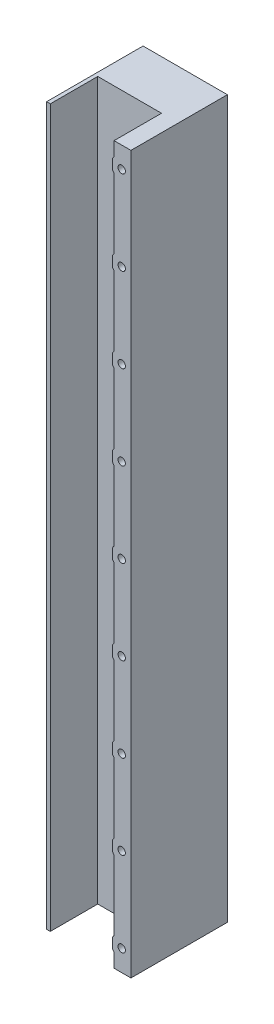
SolidWorks part; units mm, degrees
ref_plane "Top" through (0, 0, 0) normal (0, 0, 1) x (1, 0, 0)
ref_plane "Front" through (0, 0, 0) normal (0, 1, 0) x (1, 0, 0)
ref_plane "Right" through (0, 0, 0) normal (1, 0, 0) x (0, 0, -1)
sketch "Profile Sketch" plane through (0.0456, 0, -0.0242) normal (0, 1, 0) x (-1, 0, 0)
  line L1 (16.0456, 0.0242) -> (0.0456, 0.0242)
  line L2 (0.0456, 0.0242) -> (0.0456, -18.2758)
  line L3 (0.0456, -18.2758) -> (16.0456, -18.2758)
  line L5 (16.0456, -18.2758) -> (16.0456, 0.0242)
  line L12 (16.0456, 0.3949) -> (16.0456, 1.3939) construction
  line L13 (1.7956, 0.0242) -> (1.7956, 4.0449) construction
  dimension "D2" = 1.75
  dimension "Reel Width" = 16
  dimension "Height" = 18.3
extrude "Profile Extrude" add sketch "Profile Sketch" along normal blind 136
sketch "Pocket Sketch" plane through (0, 0, 0) normal (0, 1, 0) x (1, 0, 0)
  line L0 (-1.75, 0) -> (-1.75, -2.6213) construction
  line L2 (-16, 0) -> (0, 0) construction
  line L4 (-15.3, 0) -> (-3.2, 0)
  line L5 (-15.3, 0) -> (-15.3, 9)
  line L6 (-15.3, 9) -> (-3.2, 9)
  line L7 (-3.2, 0) -> (-3.2, 9)
  point P9 (-9.25, 0)
  dimension "D1" = 1.75
  dimension "Width" = 12.1
  dimension "Depth" = 9
  dimension "Center From Pins" = 7.5
extrude "Pocket Cut" cut sketch "Pocket Sketch" along normal through all
sketch "Index Hole Sketch" plane through (0, 0, 0) normal (0, 0, 1) x (1, 0, 0)
  circle A0 centre (-1.75, 4) radius 0.7
  dimension "D2" = 1.4
  dimension "D3" = 4
  dimension "D1" = 1.75
extrude "First Index Hole Cut" cut sketch "Index Hole Sketch" against normal blind 8
sketch "Index Hole Reinforcement Sketch" plane through (0, 0, 0) normal (0, 0, 1) x (1, 0, 0)
  line L0 (-3.5, 4.9682) -> (-3.5, 3.0318)
  line L1 (-3.2, 5.3775) -> (-3.2, 2.6225)
  line L2 (-3.2, 136) -> (-3.2, 0) construction
  arc A0 (-3.2, 5.3775) -> (-3.5, 4.9682) centre (-1.75, 4) ccw
  arc A1 (-3.5, 3.0318) -> (-3.2, 2.6225) centre (-1.75, 4) ccw
  dimension "D1" = 2
  dimension "D2" = 1.75
extrude "Index Hole Reinforcement" add sketch "Index Hole Reinforcement Sketch" against normal up to next
pattern_linear "Index Hole Pattern" count 9 spacing 16 along (0, 1, 0) of "First Index Hole Cut", "Index Hole Reinforcement"
ref_plane "Mid Plane" through (0, 68, 0) normal (0, -1, 0) x (-1, 0, 0)
equation "\"D2@Index Hole Sketch\" = 1.40mm"
